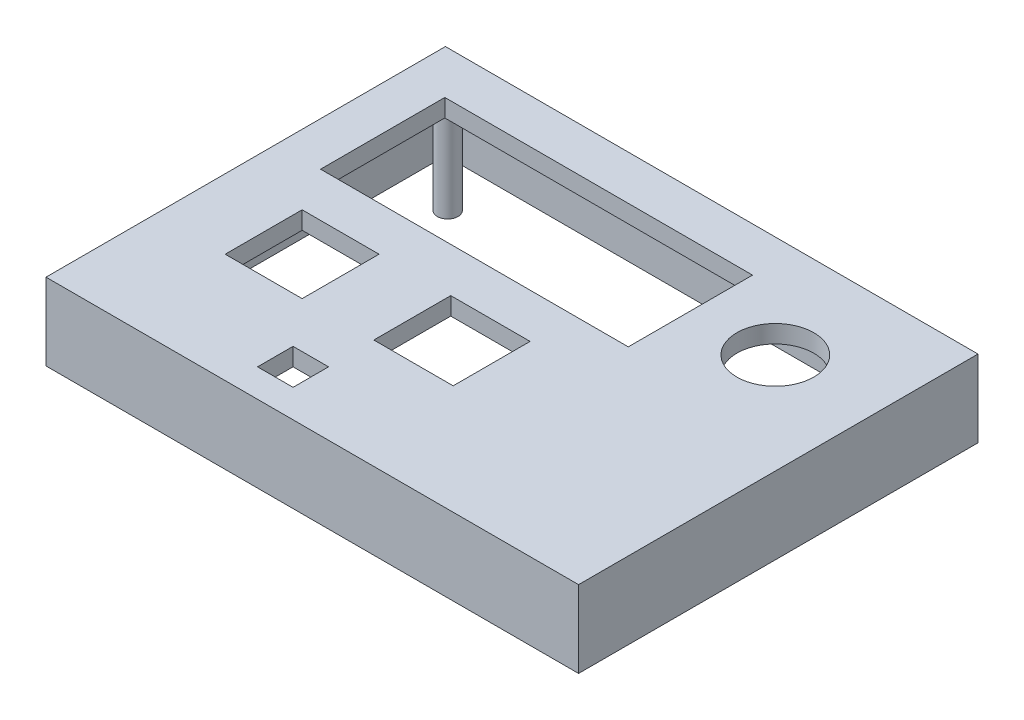
SolidWorks part; units mm, degrees
ref_plane "Front Plane" through (0, 0, 0) normal (0, 0, 1) x (1, 0, 0)
ref_plane "Top Plane" through (0, 0, 0) normal (0, 1, 0) x (1, 0, 0)
ref_plane "Right Plane" through (0, 0, 0) normal (1, 0, 0) x (0, 0, -1)
sketch "Sketch1" plane through (0, 0, 0) normal (0, 1, 0) x (1, 0, 0)
  line L0 (-8.1, -15.25) -> (5.3066, -15.25)
  line L1 (-45, -33.75) -> (45, -33.75)
  line L2 (-45, -33.75) -> (-45, 33.75)
  line L3 (-45, 33.75) -> (45, 33.75)
  line L4 (45, -33.75) -> (45, 33.75)
  line L5 (-45, -33.75) -> (45, 33.75) construction
  line L6 (-45, 33.75) -> (45, -33.75) construction
  line L7 (-8.1, -15.25) -> (-8.1, -2.25)
  line L8 (-8.1, -2.25) -> (5.3066, -2.25)
  line L9 (-37.6, 26.25) -> (14.4, 26.25)
  line L10 (-37.6, 26.25) -> (-37.6, 5.25)
  line L11 (-37.6, 5.25) -> (14.4, 5.25)
  line L12 (14.4, 26.25) -> (14.4, 5.25)
  line L13 (-33.217, -15.25) -> (-20.217, -15.25)
  line L14 (-33.217, -15.25) -> (-33.217, -2.25)
  line L15 (-33.217, -2.25) -> (-20.217, -2.25)
  line L16 (-20.217, -15.25) -> (-20.217, -2.25)
  line L21 (-45, -33.75) -> (-11, -33.75)
  line L22 (5.3066, -15.25) -> (5.3066, -2.25)
  line L23 (-11, -33.75) -> (-45, -33.75)
  line L24 (-11, -29) -> (-14, -29)
  line L25 (-14, -29) -> (-14, -23)
  line L26 (-14, -23) -> (-8, -23)
  line L27 (-8, -23) -> (-8, -29)
  line L28 (-8, -29) -> (-11, -29)
  circle A0 centre (28, 16.5) radius 6.5
  point P0 (0, 0)
  point P13 (0, 0)
  point P27 (0, 0)
  dimension "D7" = 13
  dimension "D1" = 90
  dimension "D2" = 67.5
  dimension "D3" = 7.5
  dimension "D4" = 13
  dimension "D5" = 52
  dimension "D6" = 21
  dimension "D8" = 13
  dimension "D9" = 7.5
  dimension "D10" = 17.25
  dimension "D11" = 29.5
  dimension "D12" = 7.75
  dimension "D13" = 7.5
  dimension "D14" = 3
  dimension "D15" = 3
  dimension "D16" = 6
  dimension "D17" = 13
extrude "Boss-Extrude1" add sketch "Sketch1" along normal blind 3 contours L1 L4 L3 L2 A0 L16 L13 L14 L15 L9 L12 L11 L10 L22 L7 L27 L28 L24 L25 L26 region at (-43.875, 0, 0)
sketch "Sketch2" plane through (0, 0, 0) normal (0, -1, 0) x (1, 0, 0)
  line L0 (-45, -33.75) -> (45, -33.75) construction
  line L1 (42, -30.75) -> (-42, -30.75)
  line L2 (42, -30.75) -> (42, 30.75)
  line L3 (42, 30.75) -> (-42, 30.75)
  line L4 (-42, -30.75) -> (-42, 30.75)
  line L5 (45, 33.75) -> (45, -33.75) construction
  line L6 (-45, 33.75) -> (45, 33.75) construction
  line L7 (-45, 33.75) -> (-45, -33.75) construction
  line L9 (45, -33.75) -> (-45, -33.75)
  line L10 (45, -33.75) -> (45, 33.75)
  line L11 (45, 33.75) -> (-45, 33.75)
  line L12 (-45, -33.75) -> (-45, 33.75)
  dimension "D1" = 3
  dimension "D2" = 3
  dimension "D3" = 3
  dimension "D4" = 3
extrude "Boss-Extrude2" add sketch "Sketch2" along normal blind 10
sketch "Sketch3" plane through (0, 0, 0) normal (0, -1, 0) x (1, 0, 0)
  line L0 (-37.6, -26.25) -> (-37.6, -5.25) construction
  line L1 (-37.6, -26.25) -> (14.4, -26.25) construction
  circle A0 centre (-38.8, -27.93) radius 1.75
  dimension "D1" = 3.5
  dimension "D2" = 1.2
  dimension "D3" = 1.68
extrude "Boss-Extrude3" add sketch "Sketch3" along normal blind 15
